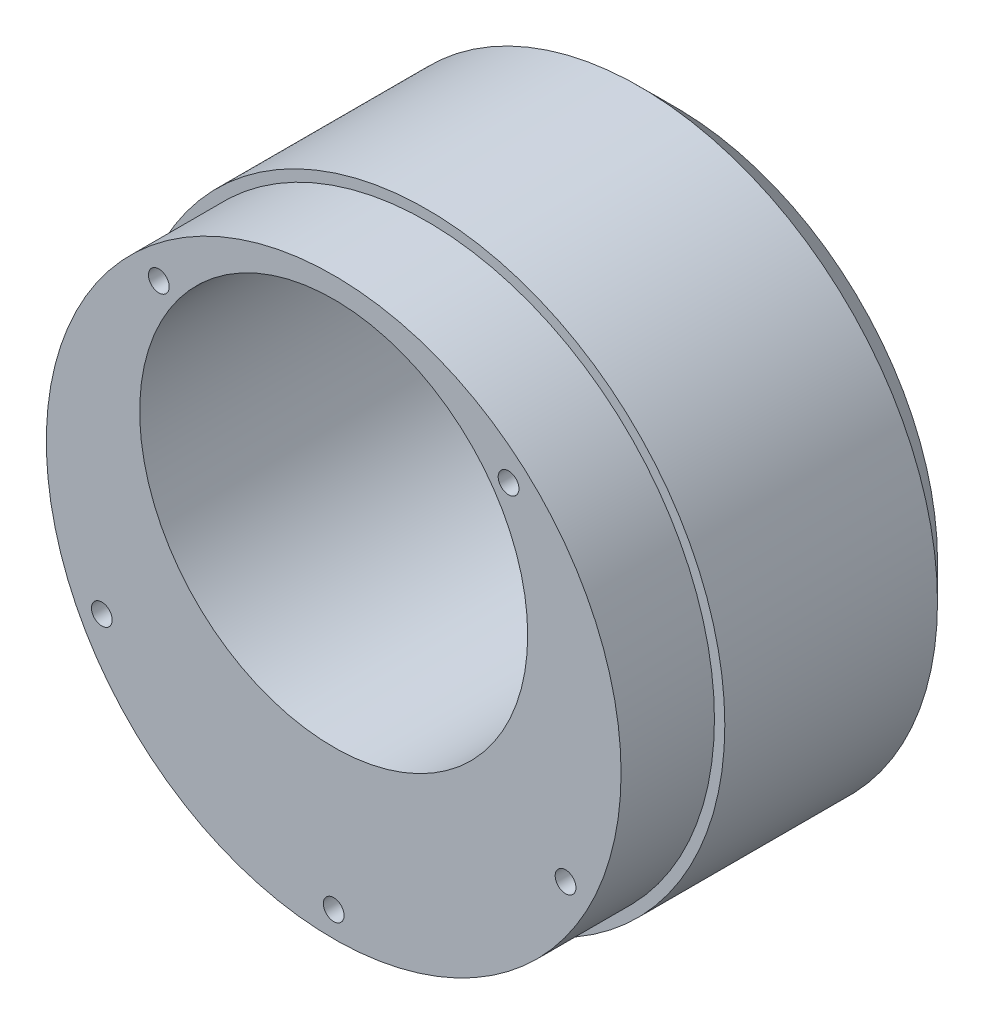
SolidWorks part; units mm, degrees
ref_plane "Спереди" through (0, 0, 0) normal (0, 0, 1) x (1, 0, 0)
ref_plane "Сверху" through (0, 0, 0) normal (0, 1, 0) x (1, 0, 0)
ref_plane "Справа" through (0, 0, 0) normal (1, 0, 0) x (0, 0, -1)
sketch "Sketch1" plane through (0, 0, 0) normal (0, 0, 1) x (1, 0, 0)
  circle A0 centre (0, 0) radius 28.7
  circle A1 centre (0, 0) radius 6.15
  circle A3 centre (0, 7) radius 15.5 construction
  circle A4 centre (15.5, 7) radius 1.65
  circle A5 centre (7.75, -6.4234) radius 1.65
  circle A6 centre (-7.75, -6.4234) radius 1.65
  circle A7 centre (-15.5, 7) radius 1.65
  circle A8 centre (-7.75, 20.4234) radius 1.65
  circle A9 centre (7.75, 20.4234) radius 1.65
  point P20 (0, 7)
  dimension "D1" = 57.4
  dimension "D2" = 12.3
  dimension "D3" = 7
  dimension "D4" = 31
  dimension "D5" = 3.3
  dimension "D6" = 6
extrude "Основа" add sketch "Sketch1" along normal blind 33
sketch "Sketch2" plane through (0, 0, 33) normal (0, 0, 1) x (1, 0, 0)
  circle A0 centre (0, 7) radius 18.7
  dimension "D1" = 37.4
  dimension "D2" = 7
extrude "Посадочное под двигатель" cut sketch "Sketch2" against normal blind 27
sketch "Sketch4" plane through (0, 0, 33) normal (0, 0, 1) x (1, 0, 0)
  circle A0 centre (0, 0) radius 27.7
  circle A1 centre (0, 0) radius 28.7
  circle A2 centre (0, 0) radius 28.7 construction
  dimension "D1" = 55.4
extrude "Вырез под внутреннее кольцо подшипника" cut sketch "Sketch4" against normal blind 9
sketch "Sketch5" plane through (0, 0, 33) normal (0, 0, 1) x (1, 0, 0)
  line L0 (0, 7) -> (0, -25.25) construction
  line L1 (-22.3482, -11.7524) -> (0, 7) construction
  line L2 (0, 7) -> (-16.8543, 18.8015) construction
  circle A1 centre (0, 7) radius 18.7 construction
  circle A3 centre (-22.3482, -11.7524) radius 1
  circle A7 centre (-16.8543, 18.8015) radius 1
  circle A12 centre (0, 0) radius 25.25 construction
  circle A13 centre (0, 7) radius 18.7 construction
  circle A14 centre (0, -25.25) radius 1
  circle A15 centre (16.8543, 18.8015) radius 1
  circle A16 centre (22.3482, -11.7524) radius 1
  dimension "D1" = 50.5
  dimension "D4" = 2
  dimension "D2" = 50
  dimension "D3" = 125
extrude "Под шурупы крепления колена" cut sketch "Sketch5" against normal blind 10
chamfer "Chamfer1" distance 3.5 angle 45 1 edges at (28.7, 0, 0)
sketch "Эскиз1" plane through (0, 0, 0) normal (0, 0, -1) x (-1, 0, 0)
  circle A0 centre (-7.75, 20.4234) radius 3
  circle A1 centre (7.75, 20.4234) radius 3
  circle A2 centre (15.5, 7) radius 3
  circle A3 centre (7.75, -6.4234) radius 3
  circle A4 centre (-7.75, -6.4234) radius 3
  circle A5 centre (-15.5, 7) radius 3
  dimension "D1" = 6
extrude "Углубления под шляпки" cut sketch "Эскиз1" against normal blind 2
chamfer "Скругления под шляпки винтов крепления двигателя к стакану" distance 1.5 angle 45 6 edges at (13.85, 7, 2) (6.1, -6.4234, 2) (-9.4, -6.4234, 2) (-17.15, 7, 2) (-9.4, 20.4234, 2) (6.1, 20.4234, 2)
